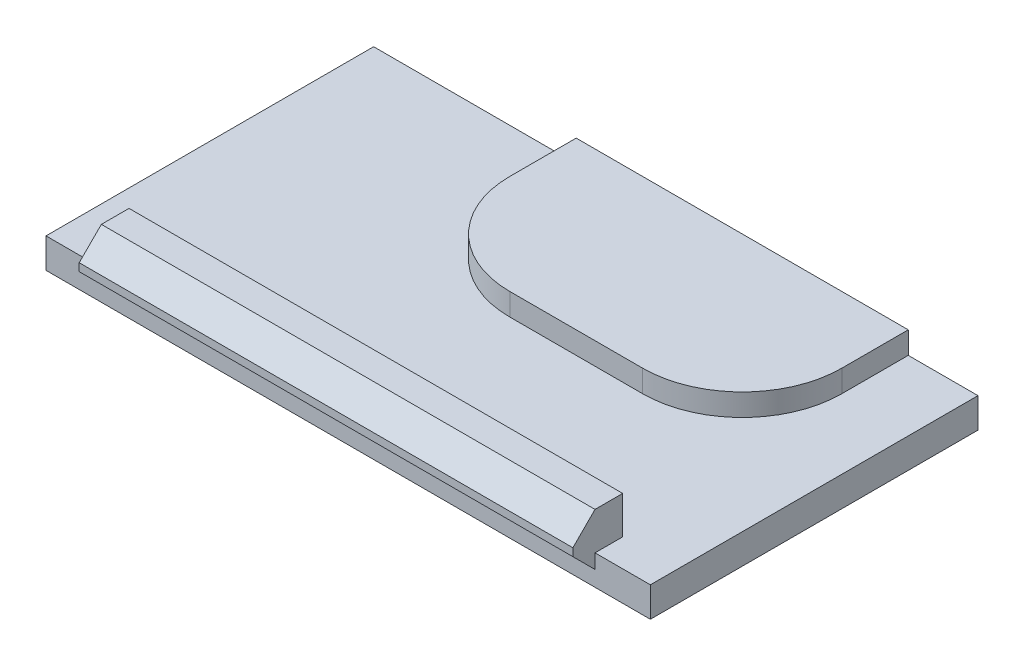
SolidWorks part; units mm, degrees
ref_plane "Front Plane" through (0, 0, 0) normal (0, 0, 1) x (1, 0, 0)
ref_plane "Top Plane" through (0, 0, 0) normal (0, 1, 0) x (1, 0, 0)
ref_plane "Right Plane" through (0, 0, 0) normal (1, 0, 0) x (0, 0, -1)
sketch "Sketch1" plane through (0, 0, 0) normal (0, 1, 0) x (1, 0, 0)
  line L1 (0, 0) -> (69.342, 0)
  line L2 (0, 0) -> (0, 37.592)
  line L3 (0, 37.592) -> (69.342, 37.592)
  line L4 (69.342, 0) -> (69.342, 37.592)
  dimension "D1" = 69.342
  dimension "D2" = 37.592
extrude "Boss-Extrude1" add sketch "Sketch1" along normal blind 3.429
sketch "Sketch3" plane through (0, 0, 0) normal (0, -1, 0) x (1, 0, 0)
  line L0 (34.671, 0) -> (34.671, -22.352) construction
  line L1 (0, 0) -> (69.342, 0) construction
  line L2 (69.342, -37.592) -> (0, -37.592) construction
  line L10 (34.671, -22.352) -> (49.911, -22.352)
  line L11 (57.531, -29.972) -> (57.531, -37.592)
  line L14 (27.051, -29.972) -> (27.051, -37.592)
  line L16 (57.531, -37.592) -> (27.051, -37.592)
  arc A2 (34.671, -22.352) -> (27.051, -29.972) centre (34.671, -29.972) ccw
  arc A3 (57.531, -29.972) -> (49.911, -22.352) centre (49.911, -29.972) ccw
  dimension "D1" = 15.24
  dimension "D3" = 7.62
  dimension "D2" = 15.24
  dimension "D4" = 7.62
  dimension "D5" = 15.24
extrude "Cut-Extrude1" cut sketch "Sketch3" against normal up to surface (3.429 mm away) up to face at (34.671, 3.429, -18.796)
sketch "Sketch5" plane through (0, 0, 0) normal (0, 0, 1) x (1, 0, 0)
  line L0 (0, 3.429) -> (0, 0) construction
  line L1 (6.35, 1.5875) -> (62.992, 1.5875)
  line L2 (6.35, 1.5875) -> (6.35, 7.9375)
  line L3 (6.35, 7.9375) -> (62.992, 7.9375)
  line L4 (62.992, 1.5875) -> (62.992, 7.9375)
  line L5 (69.342, 3.429) -> (69.342, 0) construction
  line L6 (0, 0) -> (69.342, 0) construction
  dimension "D1" = 6.35
  dimension "D2" = 6.35
  dimension "D3" = 1.5875
  dimension "D4" = 6.35
extrude "Boss-Extrude3" add sketch "Sketch5" along normal blind 2.54
chamfer "Chamfer1" distance 2.7305 angle 45 2 edges at (34.671, 1.5875, 2.54) (34.671, 7.9375, 2.54)
sketch "Sketch6" plane through (0, 0, 0) normal (0, 0, -1) x (-1, 0, 0)
  line L5 (-62.992, 7.747) -> (-6.35, 7.747)
  line L6 (-62.992, 7.747) -> (-62.992, 3.429)
  line L7 (-62.992, 3.429) -> (-6.35, 3.429)
  line L8 (-6.35, 7.747) -> (-6.35, 3.429)
extrude "Boss-Extrude4" add sketch "Sketch6" along normal blind 3.175
sketch "Sketch7" plane through (0, 0, 0) normal (0, -1, 0) x (1, 0, 0)
  line L0 (0, -9.017) -> (69.342, -9.017) construction
  line L1 (0, -37.592) -> (0, 0) construction
  line L2 (69.342, 0) -> (69.342, -37.592) construction
  line L4 (49.911, -22.352) -> (34.671, -22.352) construction
  text T0 "<b>BATTERY</b>" font "Arial Rounded MT Bold" height 6.35
  dimension "D1" = 13.335
extrude "Cut-Extrude2" cut sketch "Sketch7" against normal blind 1.016
sketch "Sketch8" plane through (0, 3.429, 0) normal (0, 1, 0) x (1, 0, 0)
  line L0 (61.341, 37.592) -> (61.341, 18.542)
  line L1 (69.342, 37.592) -> (57.531, 37.592) construction
  line L2 (34.671, 18.542) -> (61.341, 18.542)
  line L3 (23.241, 29.972) -> (23.241, 37.592)
  line L4 (27.051, 37.592) -> (0, 37.592) construction
  line L5 (27.051, 29.972) -> (27.051, 37.592) construction
  line L6 (57.531, 37.592) -> (57.531, 29.972) construction
  line L11 (49.911, 22.352) -> (34.671, 22.352) construction
  line L12 (61.341, 37.592) -> (23.241, 37.592)
  arc A0 (23.241, 29.972) -> (34.671, 18.542) centre (34.671, 29.972) ccw
  arc A1 (27.051, 29.972) -> (34.671, 22.352) centre (34.671, 29.972) ccw construction
  arc A2 (49.911, 18.542) -> (61.341, 29.972) centre (49.911, 29.972) ccw
  arc A3 (49.911, 22.352) -> (57.531, 29.972) centre (49.911, 29.972) ccw construction
  line M8 (69.342, 37.592) -> (57.531, 37.592)
  line M9 (57.531, 37.592) -> (57.531, 29.972)
  arc M10 (57.531, 29.972) -> (49.911, 22.352) centre (49.911, 29.972) cw
  line M11 (49.911, 22.352) -> (34.671, 22.352)
  arc M12 (34.671, 22.352) -> (27.051, 29.972) centre (34.671, 29.972) cw
  line M13 (27.051, 29.972) -> (27.051, 37.592)
  line M14 (27.051, 37.592) -> (0, 37.592)
  dimension "D1" = 3.81
  dimension "D2" = 3.81
  dimension "D3" = 3.81
extrude "Boss-Extrude5" add sketch "Sketch8" along normal blind 2.54 contours L2 A2 L0 L3 A0 M8 M9 M10 M11 M12 M13 M14 | L12 M9 M13 M12 M11 M10 region at (60.915, 3.429, -33.782) region at (42.291, 3.429, -30.3075)
sketch "Sketch9" plane through (0, 3.429, 0) normal (0, -1, 0) x (1, 0, 0)
  line L0 (27.051, -37.592) -> (57.531, -37.592)
  line L1 (57.531, -37.592) -> (57.531, -29.972)
  line L2 (49.911, -22.352) -> (34.671, -22.352)
  line L3 (27.051, -37.592) -> (27.051, -29.972)
  arc A0 (27.051, -29.972) -> (34.671, -22.352) centre (34.671, -29.972) cw
  arc A1 (57.531, -29.972) -> (49.911, -22.352) centre (49.911, -29.972) ccw
  arc A2 (34.671, -22.352) -> (27.051, -29.972) centre (34.671, -29.972) ccw construction
  arc A3 (57.531, -29.972) -> (49.911, -22.352) centre (49.911, -29.972) ccw construction
extrude "Cut-Extrude3" cut sketch "Sketch9" against normal blind 0.635
